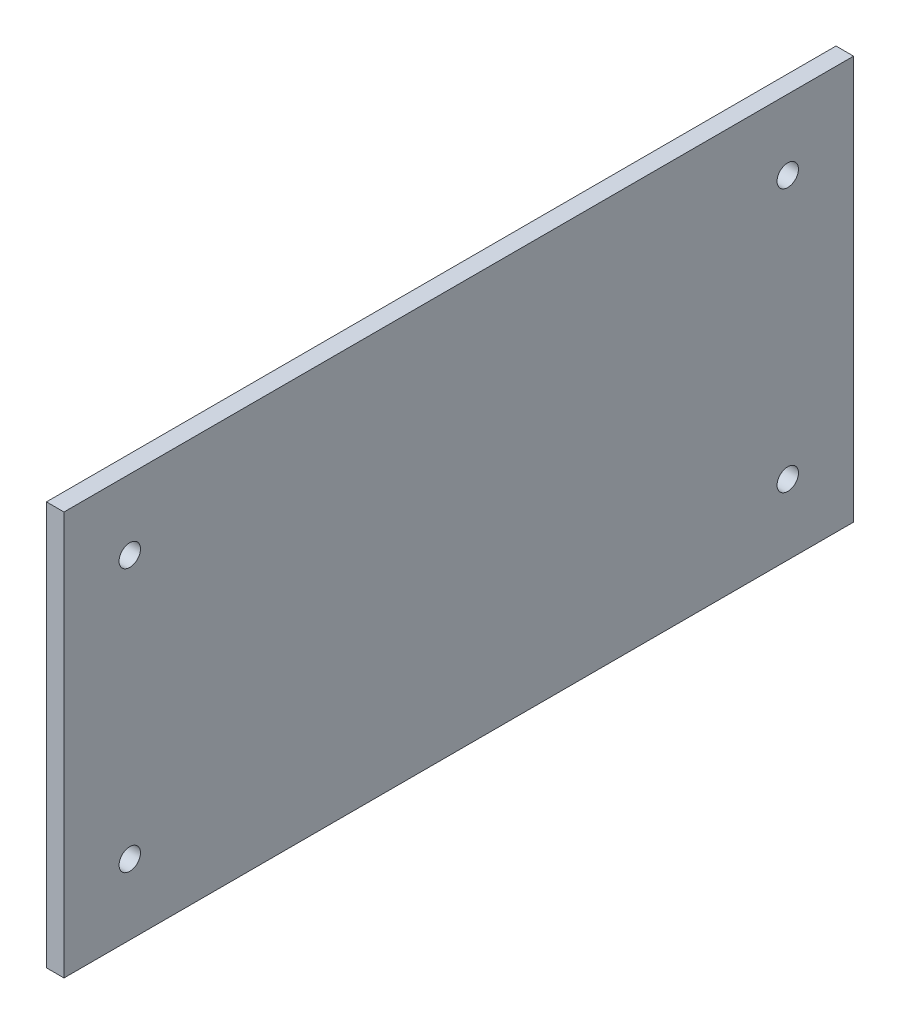
SolidWorks part; units mm, degrees
material "PCB (FR-4)"
ref_plane "Front Plane" through (0, 0, 0) normal (0, 0, 1) x (1, 0, 0)
ref_plane "Top Plane" through (0, 0, 0) normal (0, 1, 0) x (1, 0, 0)
ref_plane "Right Plane" through (0, 0, 0) normal (1, 0, 0) x (0, 0, -1)
sketch "Sketch1" plane through (0, 0, 0) normal (1, 0, 0) x (0, 0, -1)
  line L1 (-45, -23) -> (45, -23)
  line L2 (-45, -23) -> (-45, 23)
  line L3 (-45, 23) -> (45, 23)
  line L4 (45, -23) -> (45, 23)
  line L5 (-45, -23) -> (45, 23) construction
  line L6 (-45, 23) -> (45, -23) construction
  point P0 (0, 0)
  dimension "D1" = 46
  dimension "D2" = 90
extrude "Boss-Extrude1" add sketch "Sketch1" along normal blind 2
sketch "Sketch2" plane through (2, 0, 0) normal (1, 0, 0) x (0, 0, -1)
  line L0 (0, 0) -> (-37.5, 0) construction
  line L1 (-37.5, 0) -> (-37.5, -15) construction
  line L2 (0, 0) -> (37.5, 0) construction
  line L3 (37.5, 0) -> (37.5, 15) construction
  line L4 (37.5, 0) -> (37.5, -15) construction
  line L5 (-37.5, 0) -> (-37.5, 15) construction
  circle A0 centre (-37.5, -15) radius 1.0922
  circle A1 centre (37.5, -15) radius 1.0922
  circle A2 centre (37.5, 15) radius 1.0922
  circle A3 centre (-37.5, 15) radius 1.0922
  dimension "D3" = 2.1844
  dimension "D1" = 37.5
  dimension "D2" = 15
  dimension "D5" = 2
  dimension "D4" = 2
hole_wizard "#2 Clearance Hole1" positions "Sketch5" profile "Sketch6" hole size "#2" standard "ANSI Inch"
sketch "Sketch5" plane through (2, 0, 0) normal (1, 0, 0) x (0, 0, -1)
  point P0 (-37.5, 15)
  point P3 (-37.5, -15)
  point P6 (37.5, -15)
  point P9 (37.5, 15)
sketch "Sketch6" plane through (2, 15, 37.5) normal (0, 1, 0) x (0, 0, -1)
  line L0 (0, 0) -> (0, 3.7326)
  line L1 (0, 3.7326) -> (1.2192, 3)
  line L2 (1.2192, 3) -> (1.2192, 0)
  line L5 (1.2192, 0) -> (0, 0)
  line L10 (0, 3.7326) -> (-1.2192, 3) construction
  line L11 (0, -6.35) -> (0, 107.95) construction
  dimension "Hole Dia." = 2.4384
  dimension "Hole Depth" = 3
  dimension "Drill Angle" = 118
